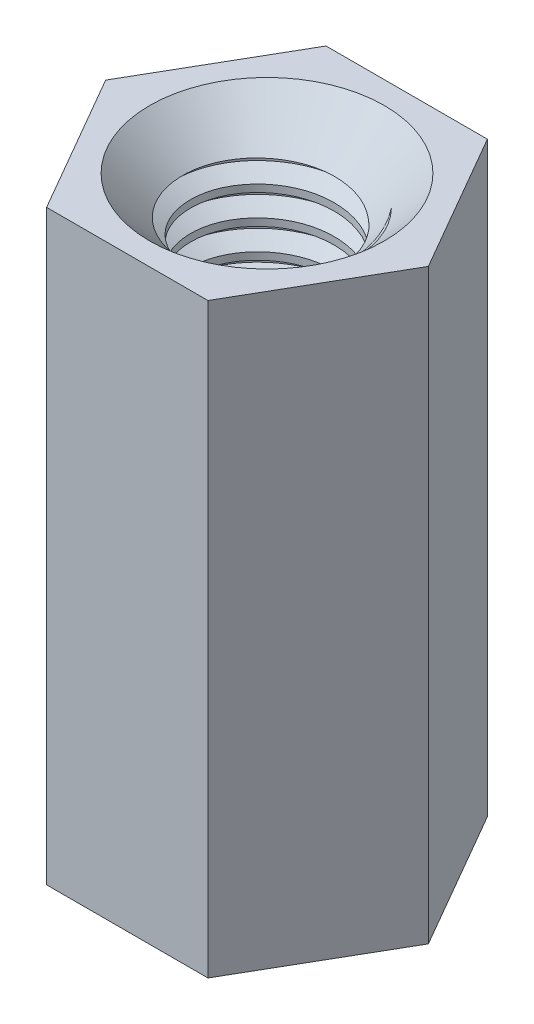
SolidWorks part; units mm, degrees
material "ABS"
ref_plane "Alzado" through (0, 0, 0) normal (0, 0, 1) x (1, 0, 0)
ref_plane "Planta" through (0, 0, 0) normal (0, 1, 0) x (1, 0, 0)
ref_plane "Vista lateral" through (0, 0, 0) normal (1, 0, 0) x (0, 0, -1)
sketch "Croquis1" plane through (0, 0, 0) normal (0, 1, 0) x (1, 0, 0)
  line L1 (2.75, 0) -> (1.375, 2.3816)
  line L2 (1.375, 2.3816) -> (-1.375, 2.3816)
  line L3 (-1.375, 2.3816) -> (-2.75, 0)
  line L4 (-2.75, 0) -> (-1.375, -2.3816)
  line L5 (-1.375, -2.3816) -> (1.375, -2.3816)
  line L6 (1.375, -2.3816) -> (2.75, 0)
  circle A0 centre (0, 0) radius 2.75 construction
extrude "Saliente-Extruir1" add sketch "Croquis1" against normal blind 10
sketch "Croquis2" plane through (0, -10, 0) normal (0, -1, 0) x (1, 0, 0)
  circle A0 centre (0, 0) radius 1.5
  dimension "D1" = 3
extrude "Cortar-Extruir1" cut sketch "Croquis2" against normal through all
thread "Rosca3" pitch 0.5 start angle 0, offset 5, length 0, pitch 0.5, diameter 3
ref_plane "Plano3" through (1.5, -15, 0) normal (0, 0, 1) x (1, 0, 0)
sketch "Perfil de rosca3" plane through (1.5, -15, 0) normal (0, 0, 1) x (1, 0, 0)
  line L0 (0, 0) -> (0, 0.5) construction
  line L11 (0, 0) -> (0, 0.4375)
  line L12 (0, 0.4375) -> (-0.2706, 0.2812)
  line L13 (-0.2706, 0.2812) -> (-0.2706, 0.1562)
  line L15 (-0.2706, 0.1562) -> (0, 0)
  line L17 (-0.2706, 0.2187) -> (0, 0.2187) construction
  point P2 (0, 0)
  dimension "Pitch" = 0.5
  dimension "Profile_Angle" = 60
  dimension "Profile_Land" = 0.125
  dimension "Profile_Height" = 0.2706
sketch "Croquis13" plane through (0, -10, 0) normal (0, -1, 0) x (1, 0, 0)
  circle A0 centre (0, 0) radius 2
  dimension "D1" = 4
extrude "Cortar-Extruir2" cut sketch "Croquis13" against normal blind 1 draft 45
sketch "Croquis14" plane through (0, 0, 0) normal (0, 1, 0) x (1, 0, 0)
  circle A0 centre (0, 0) radius 2
  dimension "D1" = 4
extrude "Cortar-Extruir3" cut sketch "Croquis14" against normal blind 1 draft 45
